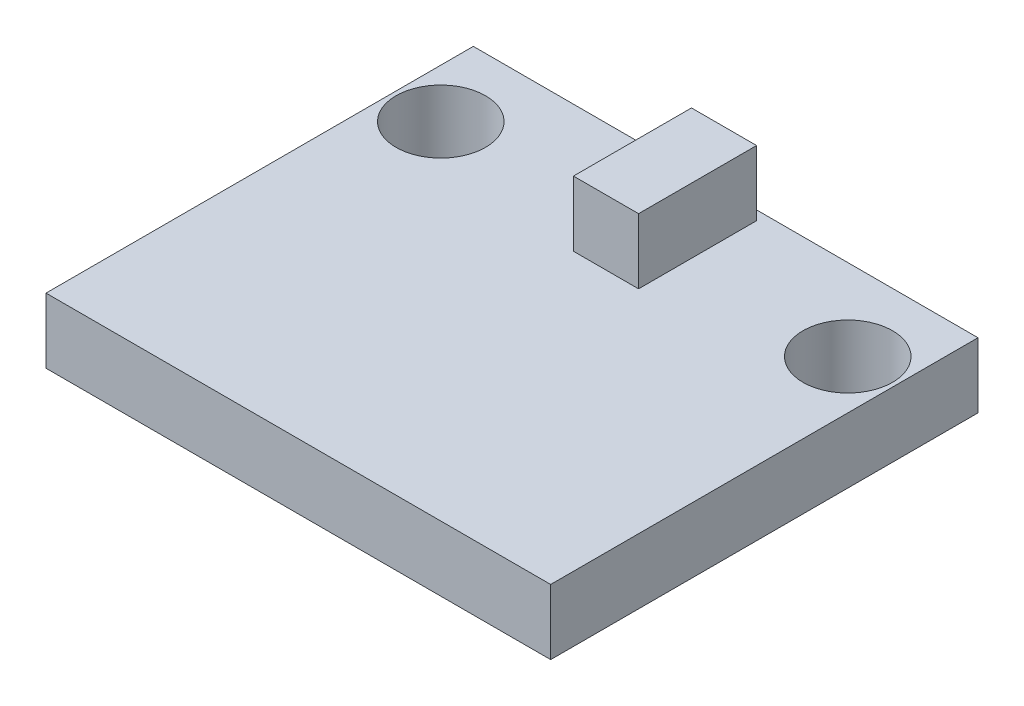
SolidWorks part; units mm, degrees
ref_plane "Front Plane" through (0, 0, 0) normal (0, 0, 1) x (1, 0, 0)
ref_plane "Top Plane" through (0, 0, 0) normal (0, 1, 0) x (1, 0, 0)
ref_plane "Right Plane" through (0, 0, 0) normal (1, 0, 0) x (0, 0, -1)
ref_axis "X Axis" through (-88.99, 0, 0) along (1, 0, 0)
ref_axis "Y Axis" through (0, 55, 0) along (0, -1, 0)
ref_axis "Z Axis" through (0, 0, -88.99) along (0, 0, 1)
sketch "Sketch1" plane through (0, 0, 0) normal (0, 1, 0) x (1, 0, 0)
  line L0 (-6.39, 0) -> (6.01, 0) construction
  line L2 (0, 1.68) -> (0, -8.82) construction
  line L3 (-6.39, 1.68) -> (6.01, 1.68)
  line L4 (-6.39, 1.68) -> (-6.39, -8.82)
  line L5 (-6.39, -8.82) -> (6.01, -8.82)
  line L6 (6.01, 1.68) -> (6.01, -8.82)
  point P9 (0, 0)
  point P10 (0, 0)
  dimension "D1" = 10.5
  dimension "D2" = 12.4
  dimension "D3" = 6.01
  dimension "D4" = 1.68
extrude "Boss-Extrude1" add sketch "Sketch1" along normal blind 1.6
sketch "Sketch2" plane through (0, 0, 0) normal (0, 1, 0) x (1, 0, 0)
  line L0 (-0.19, 1.68) -> (-0.19, -8.82) construction
  line L1 (6.01, 1.68) -> (-6.39, 1.68) construction
  line L2 (-6.39, -8.82) -> (6.01, -8.82) construction
  line L3 (6.01, -8.82) -> (6.01, 1.68) construction
  circle A0 centre (4.81, -0.32) radius 1.1
  circle A1 centre (-5.19, -0.32) radius 1.1
  dimension "D1" = 2.2
  dimension "D2" = 1.2
  dimension "D3" = 2
extrude "Cut-Extrude1" cut sketch "Sketch2" along normal through all
sketch "Sketch3" plane through (0, 1.6, 0) normal (0, 1, 0) x (1, 0, 0)
  line L1 (-0.8, -1.45) -> (0.8, -1.45)
  line L2 (-0.8, -1.45) -> (-0.8, 1.45)
  line L3 (-0.8, 1.45) -> (0.8, 1.45)
  line L4 (0.8, -1.45) -> (0.8, 1.45)
  line L5 (-0.8, -1.45) -> (0.8, 1.45) construction
  line L6 (-0.8, 1.45) -> (0.8, -1.45) construction
  point P0 (0, 0)
  dimension "D1" = 2.9
  dimension "D2" = 1.6
extrude "Boss-Extrude2" add sketch "Sketch3" along normal blind 1.6 separate body
